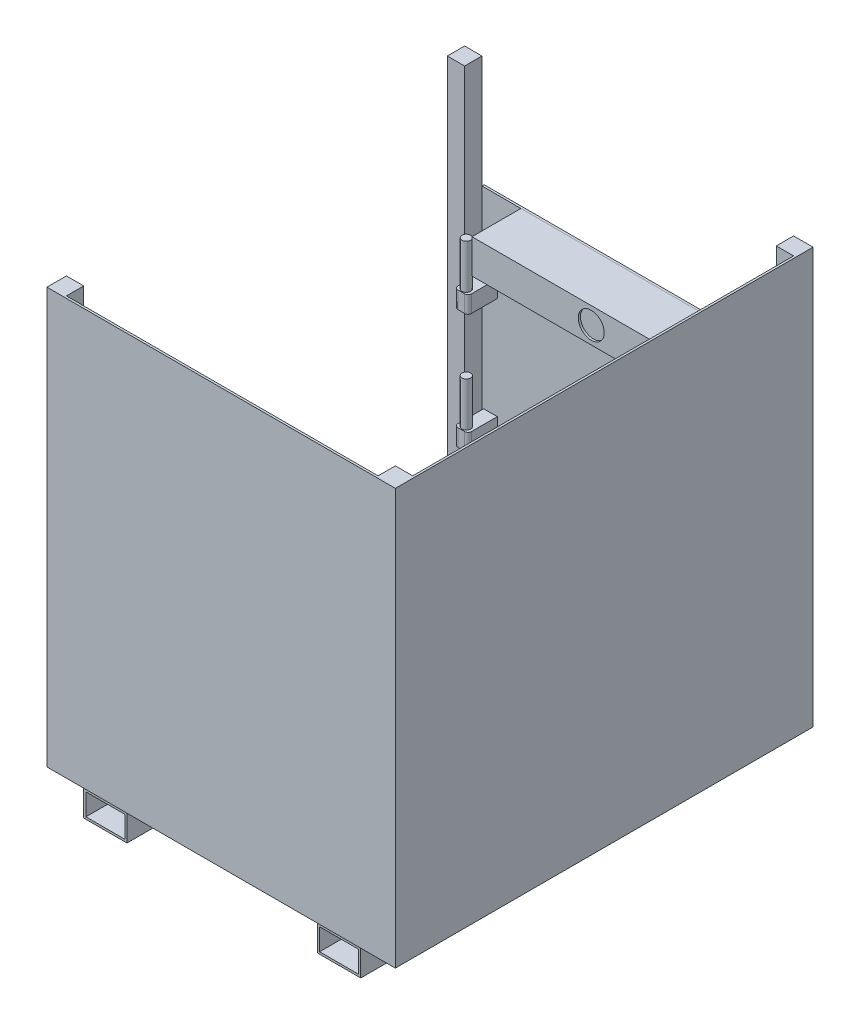
SolidWorks part; units mm, degrees
ref_plane "Front Plane" through (0, 0, 0) normal (0, 0, 1) x (1, 0, 0)
ref_plane "Top Plane" through (0, 0, 0) normal (0, 1, 0) x (1, 0, 0)
ref_plane "Right Plane" through (0, 0, 0) normal (1, 0, 0) x (0, 0, -1)
sketch "Sketch1" plane through (0, 0, 0) normal (0, 1, 0) x (1, 0, 0)
  line L1 (0, 0) -> (1016, 0)
  line L2 (0, 0) -> (0, 2438.4)
  line L3 (0, 2438.4) -> (1016, 2438.4)
  line L4 (1016, 0) -> (1016, 2438.4)
  dimension "D1" = 2438.4
  dimension "D2" = 1016
sketch "Sketch3" plane through (0, 0, 0) normal (0, 1, 0) x (1, 0, 0)
  line L0 (0, 0) -> (0, 2438.4) construction
  line L1 (0, 0) -> (50.8, 0)
  line L2 (0, 0) -> (0, 50.8)
  line L3 (0, 50.8) -> (50.8, 50.8)
  line L4 (50.8, 0) -> (50.8, 50.8)
  line L5 (1016, 0) -> (965.2, 0)
  line L6 (1016, 0) -> (1016, 50.8)
  line L7 (1016, 50.8) -> (965.2, 50.8)
  line L8 (965.2, 0) -> (965.2, 50.8)
  line L9 (0, 1219.2) -> (50.8, 1219.2)
  line L10 (0, 1219.2) -> (0, 1168.4)
  line L11 (0, 1168.4) -> (50.8, 1168.4)
  line L12 (50.8, 1219.2) -> (50.8, 1168.4)
  line L13 (0, 0) -> (1016, 0) construction
  line L14 (1016, 0) -> (1016, 2438.4) construction
  line L15 (1016, 1219.2) -> (965.2, 1219.2)
  line L16 (1016, 1219.2) -> (1016, 1168.4)
  line L17 (1016, 1168.4) -> (965.2, 1168.4)
  line L18 (965.2, 1219.2) -> (965.2, 1168.4)
  dimension "D5" = 50.8
  dimension "D7" = 1219.2
extrude "Boss-Extrude1" add sketch "Sketch3" along normal blind 1219.2
sketch "Sketch4" plane through (1016, 0, 0) normal (1, 0, 0) x (0, 0, -1)
  line L0 (0, 0) -> (2438.4, 0) construction
  line L1 (0, 1219.2) -> (1219.2, 1219.2)
  line L2 (0, 1219.2) -> (0, 0)
  line L3 (0, 0) -> (1219.2, 0)
  line L4 (1219.2, 1219.2) -> (1219.2, 0)
extrude "Boss-Extrude2" add sketch "Sketch4" along normal blind 6.35
sketch "Sketch5" plane through (0, 0, 0) normal (-1, 0, 0) x (0, 0, 1)
  line L2 (-1158.4, 500.3309) -> (-1158.4, 1039.3124)
  line L3 (-1062.3445, 1549.4) -> (-60.8, 1549.4)
  line L4 (-60.8, 0) -> (-60.8, 1549.4)
  line L5 (-1168.4, 1219.2) -> (-1168.4, 0) construction
  line L7 (-50.8, 1219.2) -> (-50.8, 0) construction
  line L8 (-957.8, 1499.4) -> (-195.8, 1499.4)
  line L9 (-957.8, 1499.4) -> (-957.8, 737.4)
  line L10 (-957.8, 737.4) -> (-195.8, 737.4)
  line L11 (-195.8, 1499.4) -> (-195.8, 737.4)
  line L12 (-1158.4, 1039.3124) -> (-1062.3445, 1549.4)
  line L13 (-1158.4, 500.3309) -> (-1097.467, 152.6674)
  line L15 (-1097.467, 152.6674) -> (-853.5655, 0)
  line L16 (-853.5655, 0) -> (-60.8, 0)
  dimension "D1" = 10
  dimension "D2" = 1549.4
  dimension "D3" = 10
  dimension "D5" = 762
  dimension "D6" = 762
  dimension "D7" = 50
  dimension "D8" = 135
sketch "Sketch6" plane through (0, 0, 0) normal (0, 0, 1) x (1, 0, 0)
  line L1 (0, 1219.2) -> (1022.35, 1219.2)
  line L2 (0, 1219.2) -> (0, 0)
  line L3 (0, 0) -> (1022.35, 0)
  line L4 (1022.35, 1219.2) -> (1022.35, 0)
extrude "Boss-Extrude4" add sketch "Sketch6" along normal blind 6.35
sketch "Sketch7" plane through (0, 0, 0) normal (0, -1, 0) x (1, 0, 0)
  line L0 (0, 0) -> (0, -2438.4) construction
  line L1 (0, -1219.2) -> (1016, -1219.2)
  line L2 (0, -1219.2) -> (0, 0)
  line L3 (0, 0) -> (1016, 0)
  line L4 (1016, -1219.2) -> (1016, 0)
extrude "Boss-Extrude7" add sketch "Sketch7" along normal blind 6 and the other way blind 0.35
sketch "Sketch8" plane through (0, 0, -1219.2) normal (0, 0, -1) x (-1, 0, 0)
  line L0 (-965.2, 1219.2) -> (-965.2, 0.35) construction
  line L1 (-965.2, 889) -> (-50.8, 889)
  line L2 (-965.2, 889) -> (-965.2, 0)
  line L3 (-965.2, 0) -> (-50.8, 0)
  line L4 (-50.8, 889) -> (-50.8, 0)
  line L5 (-50.8, 1219.2) -> (-50.8, 0.35) construction
  line L8 (-1022.35, 0) -> (-1016, 0) construction
  dimension "D1" = 889
extrude "Boss-Extrude8" add sketch "Sketch8" along normal blind 6.35 separate body
sketch "Sketch11" plane through (965.2, 0, 0) normal (-1, 0, 0) x (0, 0, 1)
  line L0 (-1225.55, 639) -> (-1075.55, 789)
  line L1 (-1225.55, 0) -> (-1225.55, 889) construction
  line L2 (-1225.55, 639) -> (-1225.55, 889)
  line L3 (-1225.55, 889) -> (-1075.55, 889)
  line L4 (-1075.55, 889) -> (-1075.55, 789)
  line L5 (-1212.85, 882.65) -> (-1081.9, 882.65)
  line L6 (-1081.9, 882.65) -> (-1081.9, 791.6303)
  line L7 (-1081.9, 791.6303) -> (-1212.85, 660.6803)
  line L8 (-1212.85, 660.6803) -> (-1212.85, 882.65)
  line L9 (-1219.2, 1219.2) -> (-1219.2, -6) construction
  dimension "D1" = 45
  dimension "D2" = 150
  dimension "D3" = 100
  dimension "D4" = 6.35
  dimension "D5" = 6.35
  dimension "D6" = 6.35
  dimension "D7" = 6.35
extrude "Boss-Extrude18" add sketch "Sketch11" along normal blind 800 separate body
sketch "Sketch12" plane through (0, 0, 0) normal (0, 0, 1) x (1, 0, 0)
  line L0 (1016, -6) -> (0, -6) construction
  line L1 (101.6, -6) -> (228.6, -6)
  line L2 (101.6, -6) -> (101.6, -82.2)
  line L3 (101.6, -82.2) -> (228.6, -82.2)
  line L4 (228.6, -6) -> (228.6, -82.2)
  line L5 (0, 0) -> (0, -6) construction
  line L10 (107.95, -75.85) -> (222.25, -75.85)
  line L11 (107.95, -75.85) -> (107.95, -12.35)
  line L12 (107.95, -12.35) -> (222.25, -12.35)
  line L13 (222.25, -75.85) -> (222.25, -12.35)
  line L14 (508, 0) -> (508, -205.6522) construction
  line L15 (0, 0) -> (1016, 0) construction
  line L16 (793.75, -75.85) -> (793.75, -12.35)
  line L17 (908.05, -12.35) -> (793.75, -12.35)
  line L18 (908.05, -75.85) -> (908.05, -12.35)
  line L19 (908.05, -75.85) -> (793.75, -75.85)
  line L20 (787.4, -6) -> (787.4, -82.2)
  line L21 (914.4, -82.2) -> (787.4, -82.2)
  line L22 (914.4, -6) -> (914.4, -82.2)
  line L23 (914.4, -6) -> (787.4, -6)
  dimension "D1" = 127
  dimension "D2" = 76.2
  dimension "D3" = 6.35
  dimension "D4" = 6.35
  dimension "D5" = 6.35
  dimension "D6" = 6.35
  dimension "D7" = 101.6
extrude "Boss-Extrude19" add sketch "Sketch12" against normal up to surface (1219.2 mm away) up to face at (610.87, 486.55, -1219.2)
sketch "Sketch17" plane through (0, 0.35, 0) normal (0, 1, 0) x (1, 0, 0)
  line L0 (323.85, 488.95) -> (323.85, 520.7)
  line L7 (323.85, 488.95) -> (355.6, 488.95)
  line L8 (355.6, 520.7) -> (355.6, 488.95)
  line L11 (692.15, 488.95) -> (660.4, 488.95)
  line L12 (660.4, 520.7) -> (660.4, 488.95)
  line L15 (323.85, 184.15) -> (355.6, 184.15)
  line L16 (355.6, 152.4) -> (355.6, 184.15)
  line L19 (692.15, 184.15) -> (660.4, 184.15)
  line L20 (660.4, 152.4) -> (660.4, 184.15)
  line L21 (323.85, 520.7) -> (355.6, 520.7)
  line L22 (660.4, 520.7) -> (692.15, 520.7)
  line L23 (692.15, 520.7) -> (692.15, 488.95)
  line L24 (355.6, 520.7) -> (660.4, 520.7) construction
  line L25 (508, 520.7) -> (508, 152.4) construction
  line L26 (965.2, 0) -> (50.8, 0) construction
  line L27 (660.4, 152.4) -> (692.15, 152.4)
  line L28 (692.15, 152.4) -> (692.15, 184.15)
  line L29 (323.85, 184.15) -> (323.85, 152.4)
  line L30 (323.85, 152.4) -> (355.6, 152.4)
  line L31 (1016, 1168.4) -> (1016, 50.8) construction
  point P20 (508, 0)
  dimension "D1" = 152.4
  dimension "D2" = 152.4
  dimension "D3" = 304.8
  dimension "D4" = 323.85
extrude "Boss-Extrude20" add sketch "Sketch17" along normal blind 457.2
sketch "Sketch18" plane through (0, 0.35, 0) normal (0, 1, 0) x (1, 0, 0)
  line L0 (0, 1168.4) -> (50.8, 1168.4) construction
  line L1 (50.8, 1168.4) -> (50.8, 1219.2) construction
  circle A0 centre (75.8, 1148.4) radius 12.7
  dimension "D1" = 25.4
  dimension "D3" = 25
  dimension "D2" = 20
extrude "Boss-Extrude21" add sketch "Sketch18" along normal blind 480 from offset 325 separate body
sketch "Sketch19" plane through (0, 0, 0) normal (-1, 0, 0) x (0, 0, 1)
  line L0 (-1135.7, 325.35) -> (-1135.7, 805.35) construction
  line L1 (-1135.7, 675.35) -> (-1161.1, 675.35)
  line L2 (-1135.7, 675.35) -> (-1135.7, 455.35)
  line L3 (-1135.7, 455.35) -> (-1161.1, 455.35)
  line L4 (-1161.1, 675.35) -> (-1161.1, 455.35)
  line L5 (-1161.1, 805.35) -> (-1161.1, 325.35) construction
  line L6 (-1135.7, 805.35) -> (-1161.1, 805.35) construction
  dimension "D1" = 130
  dimension "D2" = 220
extrude "Cut-Extrude3" cut sketch "Sketch19" against normal blind 100
sketch "Sketch20" plane through (0, 675.35, 0) normal (0, -1, 0) x (1, 0, 0)
  line L0 (50.8, -1219.2) -> (965.2, -1219.2) construction
  line L1 (95.8, -1219.2) -> (55.8, -1219.2)
  line L2 (95.8, -1219.2) -> (95.8, -1143.4)
  line L3 (85.8, -1133.4) -> (65.8, -1133.4)
  line L4 (55.8, -1219.2) -> (55.8, -1143.4)
  circle A0 centre (75.8, -1148.4) radius 12.7 construction
  arc A1 (65.8, -1133.4) -> (55.8, -1143.4) centre (65.8, -1143.4) ccw
  arc A2 (95.8, -1143.4) -> (85.8, -1133.4) centre (85.8, -1143.4) ccw
  dimension "D1" = 15
  dimension "D2" = 20
  dimension "D3" = 20
  dimension "D4" = 10
extrude "Boss-Extrude23" add sketch "Sketch20" along normal blind 50 separate body
extrude "Boss-Extrude25" add sketch "Sketch20<2>" along normal blind 50 from surface separate body starting at face at (75.8, 325.35, -1135.7)
sketch "Sketch20<2>" plane through (0, 675.35, 0) normal (0, -1, 0) x (1, 0, 0) same geometry as "Sketch20"
sketch "Sketch21" plane through (0, 0, -1075.55) normal (0, 0, 1) x (1, 0, 0)
  line L0 (165.2, 789) -> (165.2, 889) construction
  line L1 (965.2, 789) -> (965.2, 889) construction
  circle A0 centre (515.2, 839) radius 38.1
  point P4 (165.2, 839)
  dimension "D1" = 76.2
  dimension "D2" = 450
extrude "Cut-Extrude4" cut sketch "Sketch21" against normal up to next (6.35 mm away)
